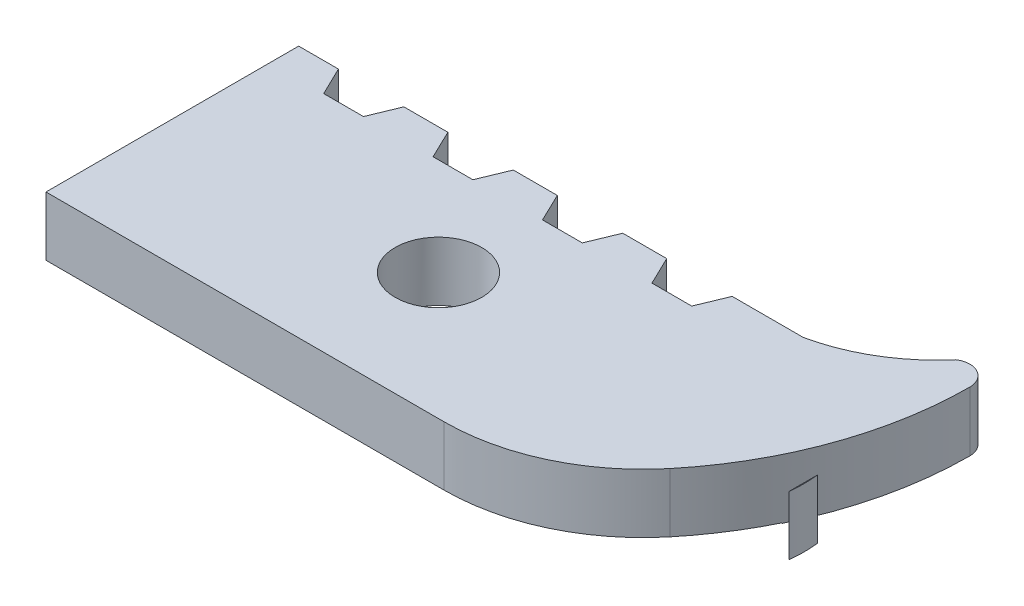
SolidWorks part; units mm, degrees
material "PET"
ref_plane "Front" through (0, 0, 0) normal (0, 0, 1) x (1, 0, 0)
ref_plane "Top" through (0, 0, 0) normal (0, 1, 0) x (1, 0, 0)
ref_plane "Right" through (0, 0, 0) normal (1, 0, 0) x (0, 0, -1)
sketch "Sketch1" plane through (0, 0, 0) normal (0, 1, 0) x (1, 0, 0)
  line L0 (-23.1719, 5.6259) -> (-23.1719, -7.0741)
  line L1 (-23.1719, 5.6259) -> (2.2281, 5.6259)
  line L3 (-23.1719, -7.0741) -> (2.2281, -7.0741)
  line L5 (-23.1719, 5.6259) -> (2.2281, -7.0741) construction
  line L6 (-23.1719, -7.0741) -> (2.2281, 5.6259) construction
  arc A1 (2.2281, 5.6259) -> (2.2281, -7.0741) centre (2.2281, -0.7241) cw
  point P4 (-10.4719, -0.7241)
  dimension "D3" = 12.7
extrude "Boss-Extrude1" add sketch "Sketch1" along normal blind 2.975
sketch "Sketch3" plane through (0, 2.975, 0) normal (0, 1, 0) x (1, 0, 0)
  line L1 (-21.1719, 5.6259) -> (-17.8821, 5.6259)
  line L2 (2.2281, 5.6259) -> (-23.1719, 5.6259) construction
  line L3 (-21.1719, 5.6259) -> (-20.4769, 4.1873)
  line L4 (-20.4769, 4.1873) -> (-18.4769, 4.1873)
  line L5 (-18.4769, 4.1873) -> (-17.8821, 5.6259)
  line L6 (-15.6719, 5.6259) -> (-12.3821, 5.6259)
  line L7 (-10.1719, 5.6259) -> (-6.8821, 5.6259)
  line L8 (-15.6719, 5.6259) -> (-14.9769, 4.1873)
  line L9 (-14.9769, 4.1873) -> (-12.9769, 4.1873)
  line L10 (-12.9769, 4.1873) -> (-12.3821, 5.6259)
  line L11 (-4.6719, 5.6259) -> (-1.3821, 5.6259)
  line L13 (-10.1719, 5.6259) -> (-9.4769, 4.1873)
  line L14 (-9.4769, 4.1873) -> (-7.4769, 4.1873)
  line L15 (-7.4769, 4.1873) -> (-6.8821, 5.6259)
  line L18 (-4.6719, 5.6259) -> (-3.9769, 4.1873)
  line L19 (-3.9769, 4.1873) -> (-1.9769, 4.1873)
  line L20 (-1.9769, 4.1873) -> (-1.3821, 5.6259)
  circle A0 centre (-9.8069, -0.7139) radius 2.175
  line M7 (2.2281, 5.6259) -> (-23.1719, 5.6259)
  dimension "D2" = 4.35
  dimension "D1" = 7.83
  dimension "D5" = 4
  dimension "D6" = 2
extrude "Cut-Extrude1" cut sketch "Sketch3" against normal blind 10 contours L4 L5 L3 M7 | L9 L10 L8 M7 | L14 L15 L13 M7 | L19 L20 L18 M7 | A0 region at (-3.004, 2.975, -4.965) region at (-8.504, 2.975, -4.965) region at (-14.004, 2.975, -4.965) region at (-19.504, 2.975, -4.965) region at (-9.8069, 2.975, 0.7139)
sketch "Sketch4" plane through (0, 2.975, 0) normal (0, 1, 0) x (1, 0, 0)
  line L20 (2.1866, 0) -> (8.5366, 0)
  line L21 (8.5366, 0) -> (8.5366, 7.65)
  line L22 (2.1866, 0) -> (2.1866, 5.6259)
  line L23 (2.2281, 5.6259) -> (-1.3821, 5.6259) construction
  arc A1 (8.5366, 7.65) -> (7.0054, 8.4972) centre (7.5366, 7.65) ccw
  arc A2 (2.2281, -7.0741) -> (2.2281, 5.6259) centre (2.2281, -0.7241) ccw construction
  arc A5 (7.0054, 8.4972) -> (2.1866, 5.6259) centre (0.3534, 14.1817) cw
  dimension "D3" = 1
  dimension "D4" = 1.75
  dimension "D5" = 8.75
  dimension "D1" = 6.35
  dimension "D2" = 7.65
extrude "Boss-Extrude2" add sketch "Sketch4" against normal blind 3
sketch "Sketch5" [suppressed] plane through (0, 0, 0) normal (0, -1, 0) x (1, 0, 0)
  line L0 (7.3819, -2.9367) -> (6.3076, 0.0762)
  line L1 (6.3076, 0.0762) -> (5.6517, 1.5014)
  line L2 (5.6517, 1.5014) -> (4.4638, 3.3564)
  line L3 (4.4638, 3.3564) -> (2.8629, 4.9344)
  line L4 (2.8629, 4.9344) -> (1.0192, 6.0821)
  line L5 (1.0192, 6.0821) -> (-1.0928, 6.8195)
  line L6 (-1.0928, 6.8195) -> (-3.3217, 7.0689)
  line L7 (-3.3217, 7.0689) -> (2.2281, 7.0741)
  line L8 (2.2281, 7.0741) -> (3.7603, 6.8865)
  line L9 (3.7603, 6.8865) -> (5.2045, 6.3334)
  line L10 (5.2045, 6.3334) -> (6.4816, 5.439)
  line L11 (6.4816, 5.439) -> (7.4841, 4.2874)
  line L12 (7.4841, 4.2874) -> (8.1885, 2.9141)
  line L13 (8.1885, 2.9141) -> (8.5435, 1.3858)
  line L14 (8.5435, 1.3858) -> (8.5214, -0.1227)
  line L15 (8.5214, -0.1227) -> (8.1237, -1.6347)
  line L18 (7.3936, -2.9691) -> (8.1237, -1.6347)
  line L19 (7.3936, -2.9691) -> (7.3819, -2.9367)
  arc A0 (5.6517, 1.5014) -> (-3.32, 7.0689) centre (-3.3123, -2.9311) ccw construction
  arc A1 (8.5366, 0) -> (2.2281, 7.0741) centre (2.2281, 0.7241) ccw construction
  parabola Q0 (8.349, -6.9213) -> (5.6517, 1.5014) focus (-7.439, -2.8103) apex (3.7093, 4.8211) construction
extrude "Cut-Extrude4" [suppressed] cut sketch "Sketch5" against normal blind 3 contours L15 L18 L19 L0 L1 L2 L3 L4 L5 L6 L7 L8 L9 L10 L11 L12 L13 L14
sketch "Sketch8" [suppressed] plane through (0, 0, 0) normal (0, -1, 0) x (1, 0, 0)
  line L0 (7.3936, -2.9691) -> (4.8173, 7.1783)
  line L7 (4.8173, 7.1783) -> (13.1491, 1.2596)
  line L8 (13.1491, 1.2596) -> (7.3936, -2.9691)
extrude "Cut-Extrude5" [suppressed] cut sketch "Sketch8" against normal blind 3 contours L7 L8 L0
sketch "Sketch9" plane through (0, 2.975, 0) normal (0, 1, 0) x (1, 0, 0)
  line L2 (-2.8127, -7.2106) -> (5.0272, -8.632)
  line L3 (5.0272, -8.632) -> (5.5042, -6.001)
  line L4 (5.5042, -6.001) -> (-2.8127, -7.2106)
extrude "Cut-Extrude6" [suppressed] cut sketch "Sketch9" against normal blind 3
sketch "Sketch10" [suppressed] plane through (0, 2.975, 0) normal (0, 1, 0) x (1, 0, 0)
  line L0 (-3.3217, -7.0689) -> (-3.3538, -7.0741)
  line L1 (-23.1719, -7.0741) -> (-1.8742, -7.0741) construction
  line L2 (-3.3538, -7.0741) -> (-1.9005, -7.1442)
  line L3 (-1.9005, -7.1442) -> (-1.7552, -7.0123)
  line L4 (-1.7552, -7.0123) -> (-3.3217, -7.0689)
extrude "Cut-Extrude7" [suppressed] cut sketch "Sketch10" against normal blind 3
sketch "Sketch11" plane through (0, 2.975, 0) normal (0, 1, 0) x (1, 0, 0)
  line L0 (8.5366, 7.65) -> (8.5366, -8.35)
  line L1 (8.5366, -8.35) -> (-1.9634, -8.35)
  arc A1 (8.5366, 7.65) -> (-1.9634, -8.35) centre (-8.9633, 7.689) cw
  point P4 (8.5366, -8.35)
  dimension "D3" = 17.5
  dimension "D1" = 16
  dimension "D2" = 10.5
extrude "Cut-Extrude8" cut sketch "Sketch11" against normal through all
fillet "Fillet1" radius 10 1 edges at (0.4335, 1.4875, 7.0741)
